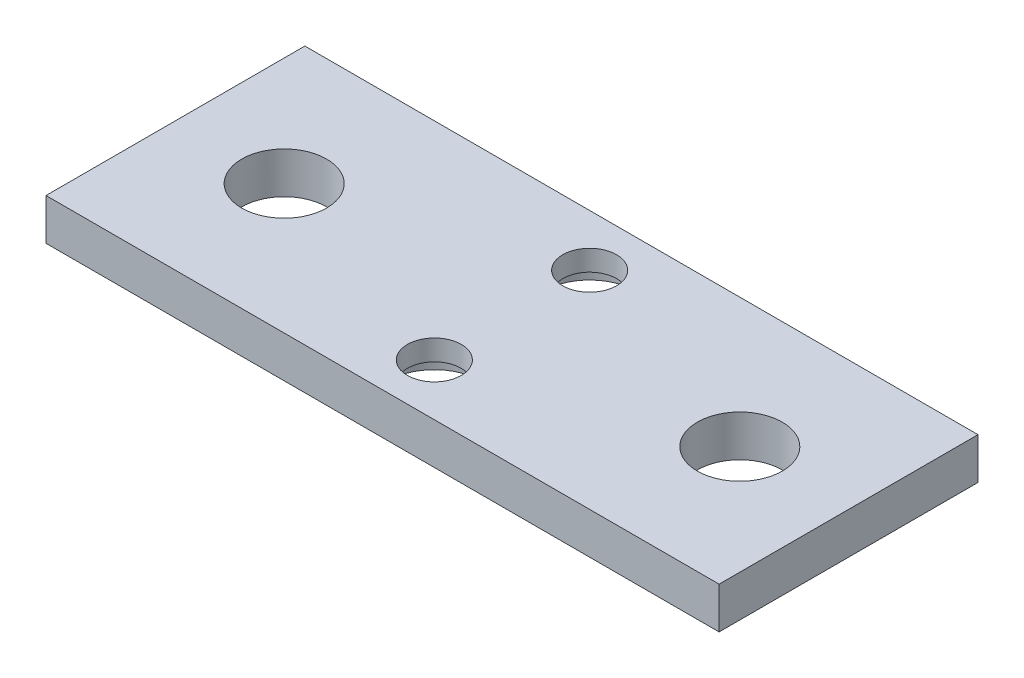
SolidWorks part; units mm, degrees
ref_plane "前视基准面" through (0, 0, 0) normal (0, 0, 1) x (1, 0, 0)
ref_plane "上视基准面" through (0, 0, 0) normal (0, 1, 0) x (1, 0, 0)
ref_plane "右视基准面" through (0, 0, 0) normal (1, 0, 0) x (0, 0, -1)
other "Configuration Table"
sketch "草图1" plane through (0, 0, 0) normal (0, 1, 0) x (1, 0, 0)
  line L1 (-32.5, 12.5) -> (32.5, 12.5)
  line L2 (-32.5, 12.5) -> (-32.5, -12.5)
  line L3 (-32.5, -12.5) -> (32.5, -12.5)
  line L4 (32.5, 12.5) -> (32.5, -12.5)
  line L5 (0, -12.5) -> (0, 12.5) construction
  line L6 (-32.5, 0) -> (32.5, 0) construction
  point P0 (0, 0)
  dimension "D1" = 25
  dimension "D2" = 65
extrude "凸台-拉伸1" add sketch "草图1" along normal blind 4
sketch "草图2" plane through (0, 4, 0) normal (0, 1, 0) x (1, 0, 0)
  line L0 (-32.5, -12.5) -> (32.5, -12.5) construction
  line L1 (-7.5, 12.5) -> (7.5, 12.5)
  line L2 (-7.5, 12.5) -> (-7.5, -12.5)
  line L3 (-7.5, -12.5) -> (7.5, -12.5)
  line L4 (7.5, 12.5) -> (7.5, -12.5)
  line L5 (0, -12.5) -> (0, 12.5) construction
  line L6 (-7.5, 0) -> (7.5, 0) construction
  point P0 (0, 0)
  dimension "D1" = 15
extrude "凸台-拉伸2" add sketch "草图2" along normal blind 13
sketch "草图3" plane through (0, 0, 0) normal (0, -1, 0) x (1, 0, 0)
  line L0 (0, 12.5) -> (0, -12.5) construction
  line L1 (-32.5, 12.5) -> (32.5, 12.5) construction
  line L2 (32.5, -12.5) -> (-32.5, -12.5) construction
  line L3 (-32.5, 0) -> (32.5, 0) construction
  line L4 (-32.5, -12.5) -> (-32.5, 12.5) construction
  line L5 (32.5, 12.5) -> (32.5, -12.5) construction
  circle A0 centre (0, -7.5) radius 2.6
  circle A1 centre (0, 7.5) radius 2.6
  circle A2 centre (-22, 0) radius 4.1
  circle A3 centre (22, 0) radius 4.1
  dimension "D1" = 5.2
  dimension "D3" = 8.2
  dimension "D2" = 5
  dimension "D4" = 22
extrude "切除-拉伸1" cut sketch "草图3" against normal through all
sketch "草图4" plane through (0, 0, 0) normal (0, -1, 0) x (1, 0, 0)
  circle A0 centre (0, -7.5) radius 4.5
  circle A1 centre (0, 7.5) radius 4.5
  dimension "D1" = 9
extrude "切除-拉伸2" cut sketch "草图4" against normal blind 2
sketch "草图5" plane through (0, 0, 12.5) normal (0, 0, 1) x (1, 0, 0)
  line L0 (7.5, 17) -> (7.5, 4) construction
  line L1 (-7.5, 4) -> (7.5, 4)
  line L2 (-7.5, 4) -> (-7.5, 8)
  line L3 (-7.5, 8) -> (7.5, 8)
  line L4 (7.5, 4) -> (7.5, 8)
  dimension "D1" = 4
extrude "凸台-拉伸3" add sketch "草图5" along normal blind 6
sketch "草图6" plane through (0, 4, 0) normal (0, -1, 0) x (1, 0, 0)
  line L0 (0, 18.5) -> (0, 12.5) construction
  line L1 (-7.5, 18.5) -> (7.5, 18.5) construction
  line L2 (-32.5, 12.5) -> (32.5, 12.5) construction
  line L3 (-7.5, 18.5) -> (-7.5, 12.5) construction
  circle A0 centre (-4.5, 15.5) radius 1.25
  circle A1 centre (4.5, 15.5) radius 1.25
  point P11 (-7.5, 15.5)
  dimension "D1" = 2.5
  dimension "D2" = 3
extrude "切除-拉伸3" cut sketch "草图6" against normal through all
ref_plane "基准面2" through (0, 0, 0) normal (0, 0, 1) x (1, 0, 0)
mirror "镜向2" about plane through (0, 0, 0) normal (0, 0, 1) of "凸台-拉伸3", "切除-拉伸3"
fillet "圆角2" radius 3 4 edges at (-7.5, 6, -18.5) (7.5, 6, -18.5) (-7.5, 6, 18.5) (7.5, 6, 18.5)
sketch "草图9" plane through (0, 0, 18.5) normal (0, 0, 1) x (1, 0, 0)
  line L1 (-7.5, 17) -> (7.5, 17)
  line L2 (-7.5, 17) -> (-7.5, 4)
  line L3 (-7.5, 4) -> (7.5, 4)
  line L4 (7.5, 17) -> (7.5, 4)
extrude "切除-拉伸4" cut sketch "草图9" against normal through all
